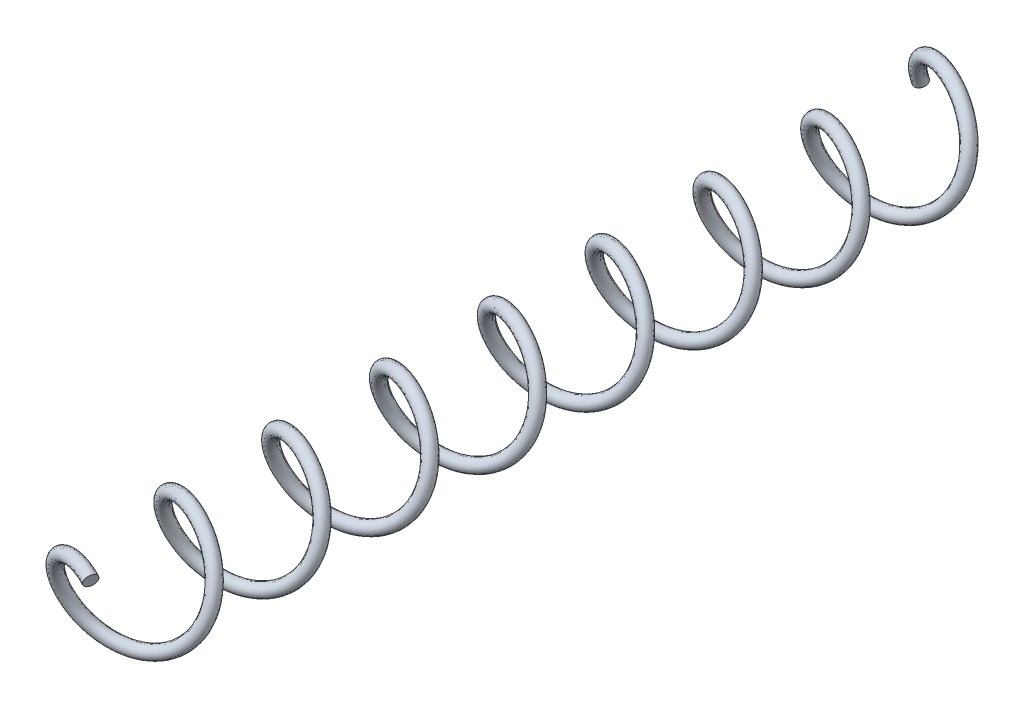
SolidWorks part; units mm, degrees
note: '?' marks a value the reader was unsure of.
material "1060 Alloy"
ref_plane "Front Plane" through (0, 0, 0) normal (0, 0, 1) x (1, 0, 0)
ref_plane "Top Plane" through (0, 0, 0) normal (0, 1, 0) x (1, 0, 0)
ref_plane "Right Plane" through (0, 0, 0) normal (1, 0, 0) x (0, 0, -1)
ref_axis "X-axis" through (-88.99, 0, 0) along (1, 0, 0)?
ref_axis "Y-axis" through (0, 55, 0) along (0, -1, 0)?
ref_axis "Z-axis" through (0, 0, -88.99) along (0, 0, 1)?
sketch "Sketch1" plane through (0, 0, 0) normal (0, 0, 1) x (1, 0, 0)
  circle A0 centre (0, 0) radius 1.4605
  dimension "D1" = 2.921
curve "Helix/Spiral1" pitch 3.175 height 26.3525 turns 8.3
sweep "Sweep1" add path "Helix/Spiral1" circular profile diameter 0.381 parameters "D3"=0.381
ref_axis "Axis1" through (0, 0, 0) along (0, 0, 1)?
